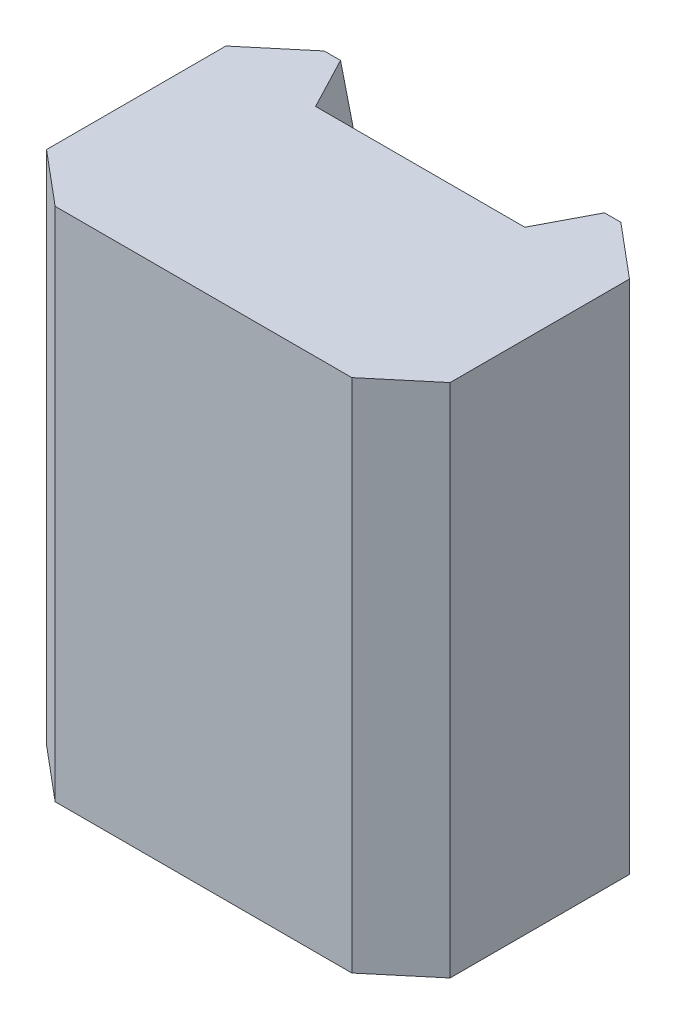
SolidWorks part; units mm, degrees
material "PET"
ref_plane "Front" through (0, 0, 0) normal (0, 0, 1) x (1, 0, 0)
ref_plane "Top" through (0, 0, 0) normal (0, 1, 0) x (1, 0, 0)
ref_plane "Right" through (0, 0, 0) normal (1, 0, 0) x (0, 0, -1)
sketch "Esquisse1" plane through (0, 0, 0) normal (0, 1, 0) x (1, 0, 0)
  line L1 (-135, -90) -> (135, -90)
  line L2 (-135, -90) -> (-135, 90)
  line L3 (-135, 90) -> (135, 90)
  line L4 (135, -90) -> (135, 90)
  line L5 (0, 90) -> (0, -90) construction
  line L6 (-135, 0) -> (135, 0) construction
  point P0 (0, 0)
  dimension "D1" = 270
  dimension "D2" = 180
extrude "Boss.-Extru.1" add sketch "Esquisse1" along normal blind 345
chamfer "Chanfrein1" distance 30 angle 50 4 edges at (-135, 172.5, -90) (-135, 172.5, 90) (135, 172.5, -90) (135, 172.5, 90) first distance on face at (-135, 172.5, 0) first distance on face at (135, 172.5, 0)
sketch "Esquisse2" plane through (0, 0, 0) normal (1, 0, 0) x (0, 0, -1)
  line L0 (55, 345) -> (255, 345)
  line L1 (-60, 345) -> (60, 345) construction
  line L2 (255, 345) -> (255, -83.9014)
  line L3 (255, -83.9014) -> (55, 345)
  dimension "D1" = 65
  dimension "D2" = 200
  dimension "D3" = 55
extrude "Enlèv. mat.-Extru.1" cut sketch "Esquisse2" against normal mid plane 180
chamfer "Chanfrein2" distance 20 angle 60 2 edges at (90, 307.4711, -72.5) (-90, 307.4711, -72.5) first distance on face at (0, 307.4711, -72.5)
